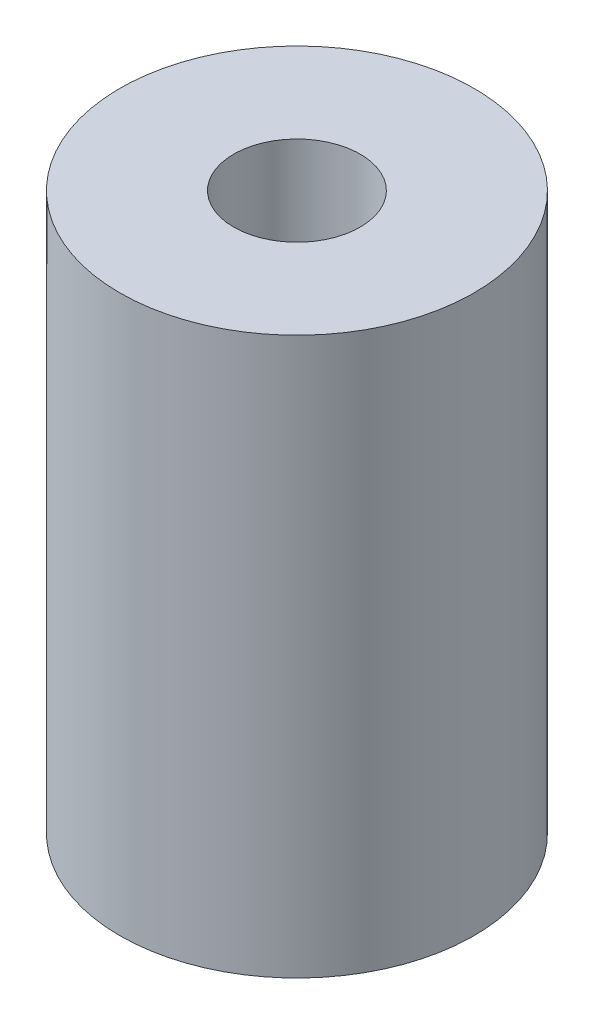
SolidWorks part; units mm, degrees
ref_plane "前视基准面" through (0, 0, 0) normal (0, 0, 1) x (1, 0, 0)
ref_plane "上视基准面" through (0, 0, 0) normal (0, 1, 0) x (1, 0, 0)
ref_plane "右视基准面" through (0, 0, 0) normal (1, 0, 0) x (0, 0, -1)
sketch "草图1" plane through (0, 0, 0) normal (0, 1, 0) x (1, 0, 0)
  circle A0 centre (0, 0) radius 7
  point P2 (0, 0)
  dimension "D1" = 14
extrude "凸台-拉伸1" add sketch "草图1" along normal blind 22
sketch "草图2" plane through (0, 22, 0) normal (0, 1, 0) x (1, 0, 0)
  circle A0 centre (0, 0) radius 2.5
  point P2 (-0.1691, 0)
  point P3 (0, 0)
  point P4 (0, 0)
  point P5 (2.2633, -2.7949)
  point P6 (3.6791, -1.9858)
  point P7 (0, 0)
  point P8 (0, 0)
  dimension "D1" = 5
extrude "切除-拉伸2" cut sketch "草图2" against normal blind 22
sketch "草图3" plane through (0, 0, 0) normal (0, -1, 0) x (1, 0, 0)
  circle A0 centre (0, 0) radius 3
  dimension "D1" = 6
extrude "切除-拉伸3" cut sketch "草图3" against normal blind 11
